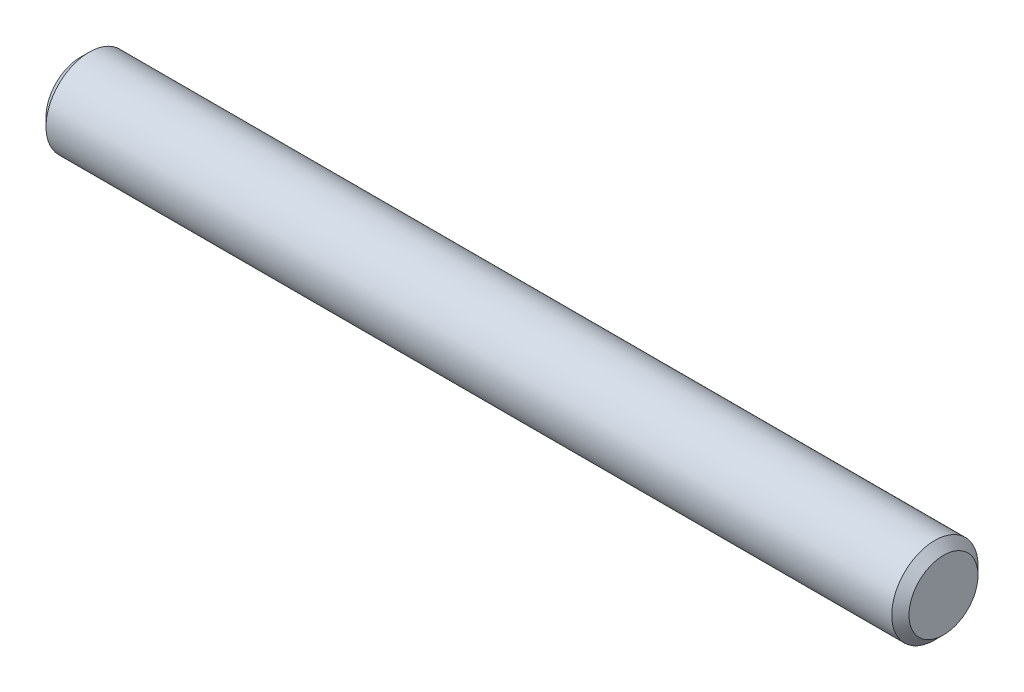
SolidWorks part; units mm, degrees
ref_plane "Front" through (0, 0, 0) normal (0, 0, 1) x (1, 0, 0)
ref_plane "Top" through (0, 0, 0) normal (0, 1, 0) x (1, 0, 0)
ref_plane "Right" through (0, 0, 0) normal (1, 0, 0) x (0, 0, -1)
sketch "Sketch1" plane through (0, 0, 0) normal (0, 0, 1) x (1, 0, 0)
  line L0 (-15.875, 0) -> (15.875, 0) construction
  line L1 (15.875, 1.5875) -> (15.875, -1.5875) construction
  line L2 (-15.875, 1.5875) -> (-15.875, -1.5875) construction
  dimension "Length" = 31.75
  dimension "Diameter" = 3.175
sketch "Sketch2" plane through (0, 0, 0) normal (1, 0, 0) x (0, 0, -1)
  circle A0 centre (0, 0) radius 1.5875
extrude "Extrude1" add sketch "Sketch2" against normal up to vertex (15.875 mm away) and the other way up to vertex (15.875 mm away) up to point (-15.875, 1.5875, 0) other way up to point (15.875, 1.5875, 0)
chamfer "Chamfer1" distance 0.3175 angle 45 2 edges at (15.875, 0, -1.5875) (-15.875, 0, -1.5875)
equation "\"D1@Chamfer1\" = \"Diameter@Sketch1\"*.1"
